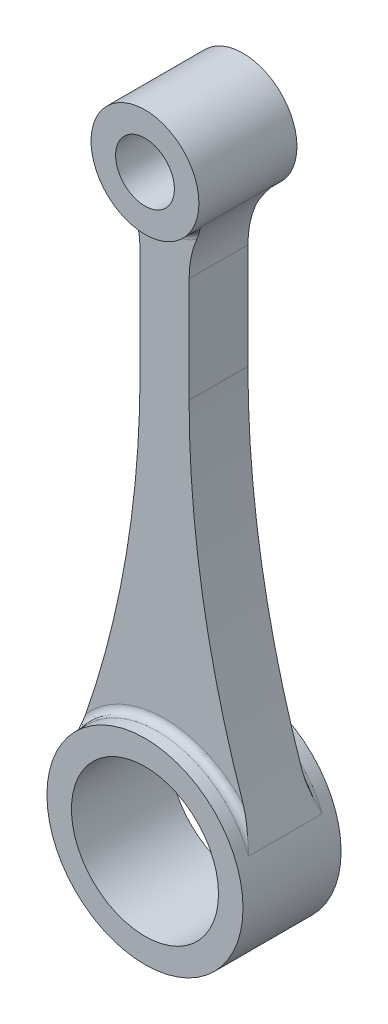
SolidWorks part; units mm, degrees
ref_plane "Front Plane" through (0, 0, 0) normal (0, 0, 1) x (1, 0, 0)
ref_plane "Top Plane" through (0, 0, 0) normal (0, 1, 0) x (1, 0, 0)
ref_plane "Right Plane" through (0, 0, 0) normal (1, 0, 0) x (0, 0, -1)
sketch "Szkic1" plane through (0, 0, 0) normal (0, 0, 1) x (1, 0, 0)
  circle A0 centre (0, 0) radius 15
  circle A1 centre (0, 0) radius 20
  circle A2 centre (0, 120) radius 6
  circle A3 centre (0, 120) radius 11
  point P7 (0, 0)
  dimension "D2" = 40
  dimension "D3" = 30
  dimension "D4" = 22
  dimension "D5" = 12
  dimension "D1" = 120
extrude "Dodanie-wyciągnięcie1" add sketch "Szkic1" along normal mid plane 20
sketch "Szkic4" plane through (0, 0, 0) normal (0, 0, 1) x (1, 0, 0)
  line L0 (0, 120) -> (0, 0) construction
  line L1 (5, 110.202) -> (5, 80.202)
  line L2 (-5, 110.202) -> (-5, 80.202)
  circle A0 centre (0, 120) radius 11 construction
  arc A1 (5, 80.202) -> (18.6481, 7.2283) centre (206.9122, 80.202) ccw
  circle A2 centre (0, 0) radius 20 construction
  arc A3 (-5, 80.202) -> (-18.6481, 7.2283) centre (-206.9122, 80.202) cw
  arc A4 (-5, 110.202) -> (5, 110.202) centre (0, 120) ccw
  arc A5 (-18.6481, 7.2283) -> (18.6481, 7.2283) centre (0, 0) cw
  dimension "D1" = 30
  dimension "D2" = 5
extrude "Dodanie-wyciągnięcie2" add sketch "Szkic4" along normal mid plane 12
fillet "Zaokrąglenie1" radius 1.5 4 edges at (0, 109, 6) (0, 109, -6) (0, 20, -6) (0, 20, 6)
fillet "Zaokrąglenie2" radius 20 2 edges at (5, 110.202, 0) (-5, 110.202, 0)
